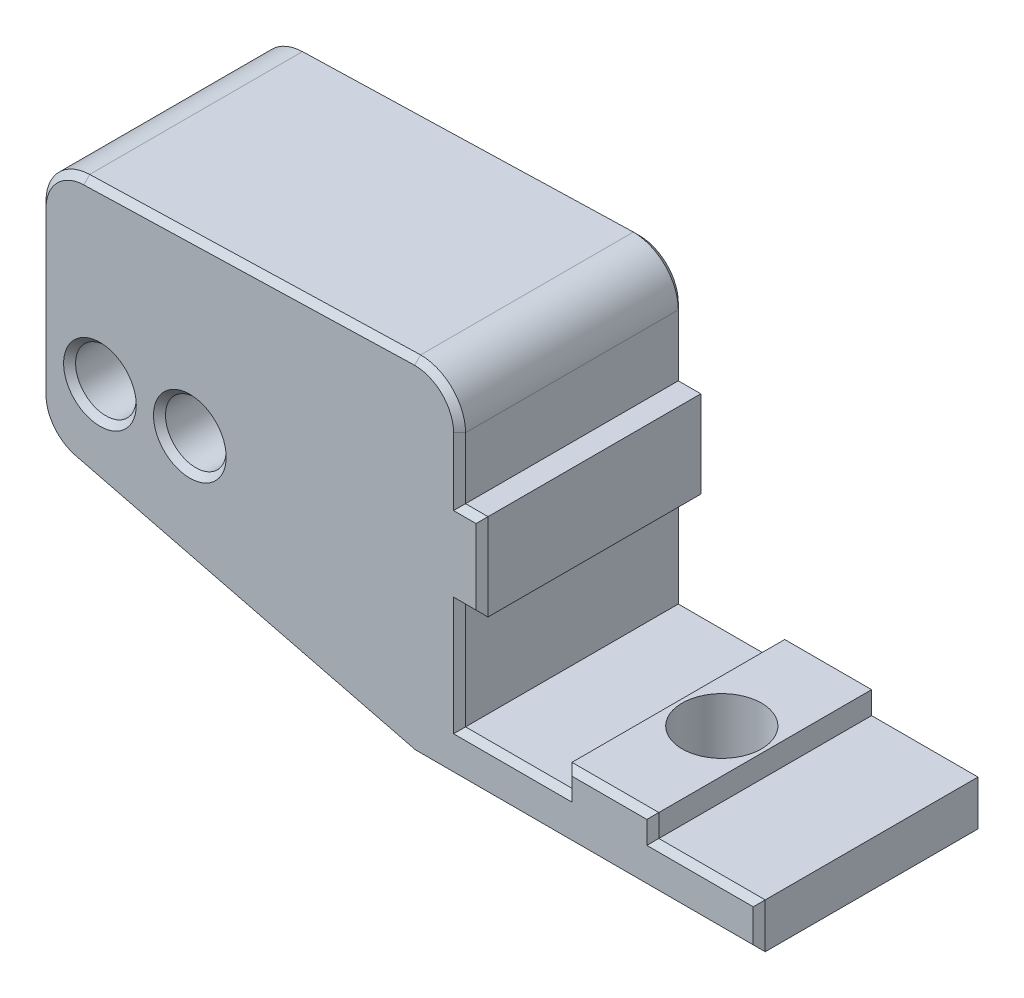
SolidWorks part; units mm, degrees
ref_plane "Front Plane" through (0, 0, 0) normal (0, 0, 1) x (1, 0, 0)
ref_plane "Top Plane" through (0, 0, 0) normal (0, 1, 0) x (1, 0, 0)
ref_plane "Right Plane" through (0, 0, 0) normal (1, 0, 0) x (0, 0, -1)
sketch "Sketch1" plane through (0, 0, 0) normal (0, 0, 1) x (1, 0, 0)
  line L0 (45.4899, -84.3159) -> (51.4899, -84.3159) construction
  line L1 (48.4899, -84.3159) -> (66.4899, -84.3159) construction
  line L2 (66.4899, -72.3159) -> (69.4899, -72.3159)
  line L3 (48.4899, -77.3159) -> (48.4899, -84.3159) construction
  line L4 (41.4899, -73.0103) -> (41.4899, -89.0659)
  line L7 (66.4899, -95.3159) -> (89.4899, -95.3159)
  line L9 (69.4899, -72.3159) -> (69.4899, -79.4159)
  line L10 (69.4899, -92.3159) -> (76.5899, -92.3159)
  line L11 (89.4899, -92.3159) -> (89.4899, -95.3159)
  line L14 (41.4899, -89.0659) -> (66.4899, -95.3159)
  line L17 (48.4899, -77.3159) -> (66.4899, -77.3159) construction
  line L18 (66.4899, -72.3159) -> (41.4899, -73.0103)
  line L19 (48.4899, -84.3159) -> (48.4899, -90.8159) construction
  line L20 (48.4899, -84.3159) -> (41.4899, -84.3159) construction
  line L21 (48.4899, -84.3159) -> (48.4899, -72.8159) construction
  line L22 (66.4899, -77.3159) -> (66.4899, -95.3159) construction
  line L23 (89.4899, 311.6195) -> (89.4899, -188.3805) construction
  line L24 (79.4899, -90.8159) -> (79.4899, -92.3159) construction
  line L26 (76.5899, -92.3159) -> (76.5899, -90.8159)
  line L27 (76.5899, -90.8159) -> (82.3899, -90.8159)
  line L28 (82.3899, -92.3159) -> (82.3899, -90.8159)
  line L29 (69.4899, -85.2159) -> (70.9899, -85.2159)
  line L31 (69.4899, -79.4159) -> (70.9899, -79.4159)
  line L32 (70.9899, -85.2159) -> (70.9899, -79.4159)
  line L33 (69.4899, -82.3159) -> (70.9899, -82.3159) construction
  line L34 (82.3899, -92.3159) -> (89.4899, -92.3159)
  line L35 (69.4899, -85.2159) -> (69.4899, -92.3159)
  circle A0 centre (48.4899, -77.3159) radius 3.025
  circle A1 centre (45.4899, -84.3159) radius 2.025
  circle A2 centre (51.4899, -84.3159) radius 2.025
  dimension "D3" = 4.05
  dimension "D4" = 6.05
  dimension "D1" = 3
  dimension "D2" = 6
  dimension "D5" = 6.5
  dimension "D6" = 7
  dimension "D7" = 11.5
  dimension "D8" = 23
  dimension "D9" = 25
  dimension "D10" = 20
  dimension "D11" = 20
  dimension "D12" = 8
  dimension "D13" = 5.8
  dimension "D14" = 1.5
extrude "Boss-Extrude1" add sketch "Sketch1" along normal blind 15
extrude "Boss-Extrude2" add sketch "Sketch1<2>" along normal up to surface (15 mm away) from offset 6 contours A0 region at (48.4899, -77.3159, 0) up to face at (47.5149, -84.3159, 15)
sketch "Sketch1<2>" plane through (0, 0, 0) normal (0, 0, 1) x (1, 0, 0) same geometry as "Sketch1"
sketch "Sketch2" plane through (0, -95.3159, 0) normal (0, -1, 0) x (1, 0, 0)
  line L0 (89.4899, 0) -> (69.4899, 15) construction
  line L1 (66.4899, 15) -> (89.4899, 15) construction
  line L2 (69.4899, 15) -> (89.4899, 15) construction
  circle A0 centre (79.4899, 7.5) radius 2.65
  dimension "D2" = 5.3
  dimension "D1" = 20
extrude "Cut-Extrude1" cut sketch "Sketch2" against normal blind 70
ref_plane "Plane1" through (0, 0, 25) normal (0, 0, 1) x (1, 0, 0)
fillet "Fillet1" radius 3 3 edges at (69.4899, -72.3159, 7.5) (41.4899, -73.0103, 7.5) (41.4899, -89.0659, 7.5)
chamfer "Chamfer1" distance 0.4 angle 45 41 edges at (53.5149, -84.3159, 0) (47.5149, -84.3159, 0) (51.5149, -77.3159, 0) (42.3394, -73.8365, 0) (41.4899, -81.3258, 0) (42.1253, -88.5698, 0) (55.1261, -92.4749, 0) (77.9899, -95.3159, 0) (89.4899, -93.8159, 0) (85.9399, -92.3159, 0) (82.3899, -91.5659, 0) (79.4899, -90.8159, 0) (76.5899, -91.5659, 0) (73.0399, -92.3159, 0) (69.4899, -88.7659, 0) (70.2399, -85.2159, 0) (70.9899, -82.3159, 0) (70.2399, -79.4159, 0) (69.4899, -77.3659, 0) (68.6112, -73.1945, 0) (55.4483, -72.6226, 0) (53.5149, -84.3159, 15) (70.2399, -79.4159, 15) (70.9899, -82.3159, 15) (70.2399, -85.2159, 15) (69.4899, -88.7659, 15) (73.0399, -92.3159, 15) (76.5899, -91.5659, 15) (79.4899, -90.8159, 15) (82.3899, -91.5659, 15) (85.9399, -92.3159, 15) (89.4899, -93.8159, 15) (77.9899, -95.3159, 15) (55.1261, -92.4749, 15) (42.1253, -88.5698, 15) (41.4899, -81.3258, 15) (42.3394, -73.8365, 15) (55.4483, -72.6226, 15) (68.6112, -73.1945, 15) (69.4899, -77.3659, 15) (47.5149, -84.3159, 15)
